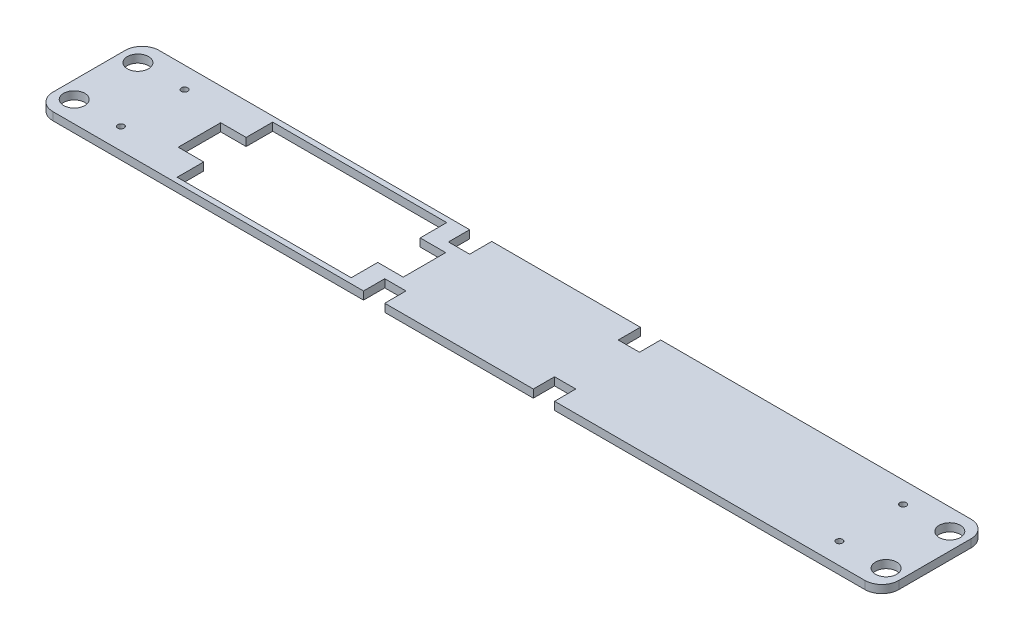
SolidWorks part; units mm, degrees
ref_plane "Front Plane" through (0, 0, 0) normal (0, 0, 1) x (1, 0, 0)
ref_plane "Top Plane" through (0, 0, 0) normal (0, 1, 0) x (1, 0, 0)
ref_plane "Right Plane" through (0, 0, 0) normal (1, 0, 0) x (0, 0, -1)
sketch "Sketch1" plane through (0, 0, 0) normal (0, 1, 0) x (1, 0, 0)
  line L0 (0, -31.75) -> (1.27, -31.75) construction
  line L1 (10.16, 0) -> (253.0475, 0)
  line L2 (0, -10.16) -> (0, -26.035)
  line L3 (10.16, -63.5) -> (253.0475, -63.5)
  line L7 (0, -43.815) -> (0, -53.34)
  line L8 (19.05, -31.75) -> (87.4324, -31.75) construction
  line L14 (0, -43.815) -> (0, -26.035)
  line L18 (253.0475, 0) -> (253.0475, -63.5)
  circle A0 centre (10.16, -50.8) radius 6.35
  circle A1 centre (10.16, -12.7) radius 6.35
  circle A3 centre (10.16, -12.7) radius 6.35 construction
  circle A4 centre (10.16, -50.8) radius 6.35 construction
  arc A5 (0, -53.34) -> (10.16, -63.5) centre (10.16, -53.34) ccw
  arc A6 (10.16, 0) -> (0, -10.16) centre (10.16, -10.16) ccw
  circle A7 centre (38.1, -50.8) radius 1.905
  circle A8 centre (38.1, -12.7) radius 1.905
  point P1 (10.16, -50.8)
  point P3 (35.8988, -50.8)
  point P9 (38.1, -50.8)
  point P22 (0, -63.5)
  point P25 (0, 0)
  point P38 (50.8, -69.85)
  dimension "D3" = 19.05
  dimension "D4" = 12.7
  dimension "D5" = 19.05
  dimension "D10" = 31.75
  dimension "D11" = 12.7
  dimension "D12" = 12.7
  dimension "D13" = 10.16
  dimension "D14" = 3.81
  dimension "D15" = 3.81
  dimension "D8" = 38.1
  dimension "D1" = 63.5
  dimension "D2" = 253.0475
  dimension "D6" = 10.16
  dimension "D7" = 10.16
  dimension "D9" = 38.1
  dimension "D16" = 12.7
extrude "Boss-Extrude1" add sketch "Sketch1" along normal blind 4.7625
mirror "Mirror1" about plane through (253.0475, 4.7625, 0) normal (-1, 0, 0) of "Boss-Extrude1"
sketch "Sketch3" plane through (0, 4.7625, 0) normal (0, 1, 0) x (1, 0, 0)
  line L0 (10.16, -63.5) -> (495.935, -63.5) construction
  line L1 (81.28, -3.175) -> (185.42, -3.175)
  line L2 (81.28, -3.175) -> (81.28, -60.325)
  line L3 (81.28, -60.325) -> (185.42, -60.325)
  line L4 (185.42, -3.175) -> (185.42, -60.325)
  line L5 (0, -10.16) -> (0, -53.34) construction
  dimension "D1" = 57.15
  dimension "D2" = 104.14
  dimension "D3" = 3.175
  dimension "D4" = 81.28
extrude "Cut-Extrude2" cut sketch "Sketch3" against normal through all
sketch "Sketch4" plane through (0, 4.7625, 0) normal (0, 1, 0) x (1, 0, 0)
  line L0 (81.28, -3.175) -> (81.28, -60.325) construction
  line L1 (66.04, -44.45) -> (200.66, -44.45)
  line L2 (66.04, -44.45) -> (66.04, -19.05)
  line L3 (66.04, -19.05) -> (200.66, -19.05)
  line L4 (200.66, -44.45) -> (200.66, -19.05)
  line L6 (185.42, -60.325) -> (185.42, -3.175) construction
  line L7 (495.935, 0) -> (10.16, 0) construction
  dimension "D1" = 15.24
  dimension "D2" = 15.24
  dimension "D3" = 25.4
  dimension "D4" = 19.05
extrude "Cut-Extrude3" cut sketch "Sketch4" against normal through all
sketch "Sketch5" plane through (0, 4.7625, 0) normal (0, 1, 0) x (1, 0, 0)
  line L0 (10.16, -63.5) -> (495.935, -63.5) construction
  line L1 (195.961, -63.5) -> (310.261, -63.5)
  line L2 (195.961, -63.5) -> (195.961, -50.8)
  line L3 (195.961, -50.8) -> (310.261, -50.8)
  line L4 (310.261, -63.5) -> (310.261, -50.8)
  line L6 (0, -10.16) -> (0, -53.34) construction
  line L7 (495.935, 0) -> (10.16, 0) construction
  line L8 (195.961, 0) -> (310.261, 0)
  line L9 (195.961, 0) -> (195.961, -12.7)
  line L10 (195.961, -12.7) -> (310.261, -12.7)
  line L11 (310.261, 0) -> (310.261, -12.7)
  dimension "D1" = 114.3
  dimension "D2" = 195.961
  dimension "D3" = 12.7
  dimension "D4" = 12.7
extrude "Cut-Extrude4" cut sketch "Sketch5" against normal blind 38.1
sketch "Sketch6" plane through (0, 4.7625, 0) normal (0, 1, 0) x (1, 0, 0)
  line L0 (310.261, -63.5) -> (495.935, -63.5) construction
  line L1 (208.661, 0.5326) -> (297.561, 0.5326)
  line L2 (208.661, 0.5326) -> (208.661, -63.5)
  line L3 (208.661, -63.5) -> (297.561, -63.5)
  line L4 (297.561, 0.5326) -> (297.561, -63.5)
  line L5 (195.961, -50.8) -> (195.961, -63.5) construction
  line L6 (310.261, -63.5) -> (310.261, -50.8) construction
  dimension "D1" = 12.7
  dimension "D2" = 12.7
extrude "Boss-Extrude2" add sketch "Sketch6" against normal up to surface (4.7625 mm away) up to face at (253.0792, 0, 31.75)
